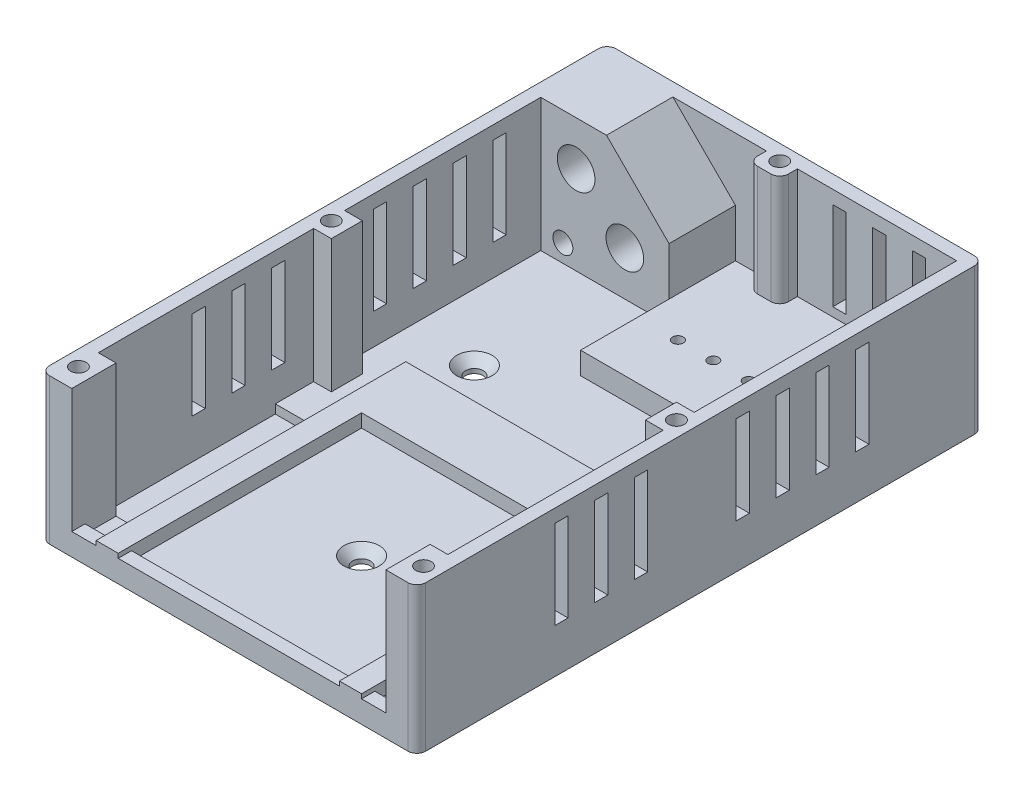
SolidWorks part; units mm, degrees
ref_plane "Front Plane" through (0, 0, 0) normal (0, 0, 1) x (1, 0, 0)
ref_plane "Top Plane" through (0, 0, 0) normal (0, 1, 0) x (1, 0, 0)
ref_plane "Right Plane" through (0, 0, 0) normal (1, 0, 0) x (0, 0, -1)
sketch "Sketch2" plane through (0, 0, 0) normal (0, 1, 0) x (1, 0, 0)
  line L1 (39.5, -62.5) -> (-39.5, -62.5)
  line L2 (39.5, -62.5) -> (39.5, 62.5)
  line L3 (39.5, 62.5) -> (-39.5, 62.5)
  line L4 (-39.5, -62.5) -> (-39.5, 62.5)
  line L5 (39.5, -62.5) -> (-39.5, 62.5) construction
  line L6 (39.5, 62.5) -> (-39.5, -62.5) construction
  point P0 (0, 0)
  dimension "D1" = 79
  dimension "D2" = 125
extrude "Boss-Extrude1" add sketch "Sketch2" along normal blind 3
sketch "Sketch9" plane through (0, 0, 0) normal (0, 1, 0) x (1, 0, 0)
  line L2 (-39.5, 62.5) -> (-39.5, -62.5)
  line L3 (-39.5, -62.5) -> (-42.5, -62.5)
  line L4 (-42.5, 65.5) -> (-42.5, -62.5)
  line L6 (39.5, 62.5) -> (39.5, -62.5)
  line L7 (39.5, -62.5) -> (42.5, -62.5)
  line L8 (42.5, 65.5) -> (42.5, -62.5)
  line L9 (39.5, 62.5) -> (-39.5, 62.5)
  line L11 (42.5, 65.5) -> (-42.5, 65.5)
  dimension "D1" = 3
  dimension "D2" = 3
  dimension "D3" = 3
sketch "Sketch3" plane through (0, 3, 0) normal (0, 1, 0) x (1, 0, 0)
  line L0 (0, -62.5) -> (0, 62.5) construction
  line L1 (-39.5, -62.5) -> (39.5, -62.5) construction
  line L2 (39.5, 62.5) -> (-39.5, 62.5) construction
  line L4 (30, -62.5) -> (-30, -62.5)
  line L5 (30, -62.5) -> (30, 7.5)
  line L6 (30, 7.5) -> (-30, 7.5)
  line L7 (-30, -62.5) -> (-30, 7.5)
  line L8 (30, -62.5) -> (-30, 7.5) construction
  line L9 (30, 7.5) -> (-30, -62.5) construction
  point P6 (0, -27.5)
  dimension "D1" = 60
  dimension "D2" = 70
extrude "support" add sketch "Sketch3" along normal blind 3
sketch "Sketch4" plane through (0, 6, 0) normal (0, 1, 0) x (1, 0, 0)
  line L0 (-30, -62.5) -> (30, -62.5) construction
  line L1 (-25, -62.5) -> (25, -62.5)
  line L2 (-25, -62.5) -> (-25, -7.5)
  line L3 (-25, -7.5) -> (25, -7.5)
  line L4 (25, -62.5) -> (25, -7.5)
  line L5 (30, 7.5) -> (-30, 7.5) construction
  line L6 (30, -62.5) -> (30, 7.5) construction
  line L7 (-30, 7.5) -> (-30, -62.5) construction
  dimension "D1" = 15
  dimension "D2" = 5
  dimension "D3" = 5
extrude "remove plastic" cut sketch "Sketch4" against normal blind 3
sketch "Sketch5" plane through (0, 3, 0) normal (0, 1, 0) x (1, 0, 0)
  line L1 (-10.5, 62.5) -> (39.5, 62.5)
  line L2 (-10.5, 62.5) -> (-10.5, 27.5)
  line L3 (-10.5, 27.5) -> (39.5, 27.5)
  line L4 (39.5, 62.5) -> (39.5, 27.5)
  line L5 (39.5, -62.5) -> (39.5, 62.5) construction
  line L7 (30, -62.5) -> (39.5, -62.5) construction
  line L8 (39.5, 62.5) -> (-39.5, 62.5) construction
  dimension "D1" = 50
  dimension "D3" = 90
extrude "Boss-Extrude3" add sketch "Sketch5" along normal blind 5
sketch "Sketch6" plane through (0, 8, 0) normal (0, 1, 0) x (1, 0, 0)
  line L0 (-10.5, 40.5) -> (39.5, 40.5) construction
  line L3 (14.5, 62.5) -> (14.5, 27.5) construction
  line L4 (39.5, 62.5) -> (-10.5, 62.5) construction
  line L5 (-10.5, 27.5) -> (39.5, 27.5) construction
  line L8 (-10.5, 27.5) -> (39.5, 27.5) construction
  circle A0 centre (-1.5, 40.5) radius 1.2
  circle A1 centre (6.5, 40.5) radius 1.2
  circle A2 centre (14.5, 40.5) radius 1.2
  circle A3 centre (22.5, 40.5) radius 1.2
  circle A4 centre (30.5, 40.5) radius 1.2
  dimension "D1" = 2.4
  dimension "D2" = 8
  dimension "D3" = 8
  dimension "D4" = 8
  dimension "D5" = 8
  dimension "D6" = 13
extrude "Cut-Extrude2" cut sketch "Sketch6" against normal blind 5 draft 1
sketch "Sketch7" plane through (0, 3, 0) normal (0, 1, 0) x (1, 0, 0)
  line L0 (-39.5, 62.5) -> (-39.5, -62.5) construction
  line L1 (-10.5, 62.5) -> (-39.5, 62.5)
  line L2 (-10.5, 62.5) -> (-10.5, 47.5)
  line L3 (-10.5, 47.5) -> (-39.5, 47.5)
  line L4 (-39.5, 62.5) -> (-39.5, 47.5)
  dimension "D1" = 15
extrude "cable block" add sketch "Sketch7" along normal blind 30
extrude "walls" add sketch "Sketch9" along normal up to surface (33 mm away) up to face at (-25, 33, -55)
sketch "Sketch8" plane through (0, 0, -47.5) normal (0, 0, 1) x (1, 0, 0)
  line L0 (-10.5, 33) -> (-10.5, 8) construction
  line L2 (-39.5, 33) -> (-10.5, 33) construction
  line L4 (-39.5, 3) -> (-10.5, 3) construction
  line L5 (-39.5, 33) -> (-39.5, 3) construction
  circle A0 centre (-20.5, 13) radius 4.25
  circle A1 centre (-34.5, 7) radius 2.25
  circle A2 centre (-31.5, 23) radius 4.25
  dimension "D1" = 8.5
  dimension "D2" = 4.5
  dimension "D3" = 10
  dimension "D8" = 10
  dimension "D4" = 8
  dimension "D5" = 10
  dimension "D6" = 5
  dimension "D7" = 4
extrude "cable holes round" cut sketch "Sketch8" against normal blind 31
sketch "Sketch10" plane through (0, 3, 0) normal (0, 1, 0) x (1, 0, 0)
  line L0 (0, -62.5) -> (0, -7.5) construction
  line L1 (-25, -62.5) -> (25, -62.5) construction
  line L2 (25, -7.5) -> (-25, -7.5) construction
  line L3 (-35.5, -62.5) -> (35.5, -62.5) construction
  line L4 (39.5, -62.5) -> (39.5, 27.5) construction
  line L5 (-39.5, -62.5) -> (-35.5, -62.5)
  line L6 (-39.5, -62.5) -> (-39.5, -52.5)
  line L7 (-39.5, -52.5) -> (-35.5, -52.5)
  line L8 (-35.5, -62.5) -> (-35.5, -52.5)
  line L9 (35.5, -62.5) -> (39.5, -62.5)
  line L10 (35.5, -62.5) -> (35.5, -52.5)
  line L11 (35.5, -52.5) -> (39.5, -52.5)
  line L12 (39.5, -62.5) -> (39.5, -52.5)
  dimension "D1" = 71
  dimension "D2" = 10
  dimension "D3" = 10
extrude "Lid screw posts front" add sketch "Sketch10" along normal up to surface (30 mm away) up to face at (-2.1, 33, -10.1)
sketch "Sketch11" plane through (0, 0, -62.5) normal (0, 0, 1) x (1, 0, 0)
  line L0 (14.5, 18) -> (32.5, 18)
  line L1 (39.5, 33) -> (39.5, 8) construction
  line L2 (14.5, 8) -> (32.5, 8)
  line L5 (39.5, 8) -> (-10.5, 8) construction
  arc A0 (14.5, 18) -> (14.5, 8) centre (14.5, 13) ccw
  arc A1 (32.5, 8) -> (32.5, 18) centre (32.5, 13) ccw
  dimension "D1" = 7
  dimension "D2" = 10
  dimension "D3" = 10
  dimension "D4" = 18
extrude "Cable cutout" [suppressed] cut sketch "Sketch11" against normal up to surface (3 mm away) up to face at (-27.25, 23, -65.5)
sketch "Sketch12" plane through (0, 0, -47.5) normal (0, 0, 1) x (1, 0, 0)
  line L0 (-24.6421, 33) -> (-10.5, 18.8579)
  line L1 (-39.5, 33) -> (-10.5, 33) construction
  line L2 (-10.5, 33) -> (-10.5, 8) construction
  line L3 (-10.5, 18.8579) -> (-10.5, 33)
  line L4 (-10.5, 33) -> (-24.6421, 33)
  dimension "D1" = 45
  dimension "D2" = 20
extrude "remove Material" cut sketch "Sketch12" against normal up to surface (15 mm away) up to face at (14.5, 20.5, -62.5)
sketch "Sketch13" plane through (0, 3, 0) normal (0, 1, 0) x (1, 0, 0)
  line L0 (-39.5, 47.5) -> (-39.5, -52.5) construction
  line L1 (-39.5, -3.8301) -> (-35.5, -3.8301)
  line L2 (-39.5, -3.8301) -> (-39.5, 3.1699)
  line L3 (-39.5, 3.1699) -> (-35.5, 3.1699)
  line L4 (-35.5, -3.8301) -> (-35.5, 3.1699)
  line L5 (39.5, -52.5) -> (39.5, 27.5) construction
  line L6 (39.5, 3.1699) -> (35.5, 3.1699)
  line L7 (39.5, 3.1699) -> (39.5, -3.8301)
  line L8 (39.5, -3.8301) -> (35.5, -3.8301)
  line L9 (35.5, 3.1699) -> (35.5, -3.8301)
  line L10 (0, -62.5) -> (0, 77.8786) construction
  line L11 (-25, -62.5) -> (25, -62.5) construction
  line L12 (39.5, 62.5) -> (-10.5, 62.5) construction
  line L13 (3.5, 58.5) -> (-3.5, 58.5)
  line L14 (3.5, 58.5) -> (3.5, 62.5)
  line L15 (3.5, 62.5) -> (-3.5, 62.5)
  line L16 (-3.5, 58.5) -> (-3.5, 62.5)
  line L17 (3.5, 58.5) -> (-3.5, 62.5) construction
  line L18 (3.5, 62.5) -> (-3.5, 58.5) construction
  point P19 (0, 60.5)
  dimension "D1" = 4
  dimension "D2" = 7
  dimension "D3" = 7
  dimension "D4" = 7
  dimension "D5" = 4
  dimension "D6" = 7
  dimension "D7" = 7
  dimension "D8" = 4
extrude "Lid screw posts back" add sketch "Sketch13" along normal up to surface (30 mm away) up to face at (-3.5203, 33, 7.7857)
sketch "Sketch14" plane through (0, 33, 0) normal (0, 1, 0) x (1, 0, 0)
  line L0 (-35.5, -62.5) -> (-42.5, -62.5) construction
  line L1 (0, 58.5) -> (0, 65.5) construction
  line L2 (42.5, -62.5) -> (35.5, -62.5) construction
  line L3 (42.5, 65.5) -> (42.5, -62.5) construction
  line L4 (39.5, -3.8301) -> (35.5, -3.8301) construction
  line L5 (-35.5, -3.8301) -> (-39.5, -3.8301) construction
  line L6 (-42.5, -62.5) -> (-42.5, 65.5) construction
  line L7 (3.5, 58.5) -> (-3.5, 58.5) construction
  line L8 (-42.5, 65.5) -> (42.5, 65.5) construction
  circle A0 centre (-39, -57.5) radius 1.75
  circle A1 centre (39, -57.5) radius 1.75
  circle A2 centre (39, -0.3301) radius 1.75
  circle A3 centre (-39, -0.3301) radius 1.75
  circle A4 centre (0, 62) radius 1.75
  dimension "D1" = 3.5
  dimension "D10" = 3.5
  dimension "D2" = 5
  dimension "D3" = 3.5
  dimension "D4" = 5
  dimension "D5" = 3.5
  dimension "D6" = 3.5
  dimension "D7" = 3.5
  dimension "D8" = 3.5
  dimension "D9" = 3.5
extrude "Lid screw holes" cut sketch "Sketch14" against normal blind 25 draft 0.5
sketch "Sketch16" plane through (0, 3, 0) normal (0, 1, 0) x (1, 0, 0)
  line L0 (-30, 7.5) -> (-30, -62.5) construction
  line L1 (-39.5, -52.5) -> (-30, -52.5)
  line L2 (-39.5, -52.5) -> (-39.5, -12.5)
  line L3 (-39.5, -12.5) -> (-30, -12.5)
  line L4 (-30, -52.5) -> (-30, -12.5)
  line L5 (30, -62.5) -> (30, 7.5) construction
  line L6 (39.5, -52.5) -> (30, -52.5)
  line L7 (39.5, -52.5) -> (39.5, -12.5)
  line L8 (39.5, -12.5) -> (30, -12.5)
  line L9 (30, -52.5) -> (30, -12.5)
  dimension "D1" = 20
  dimension "D2" = 20
extrude "Sliders" cut sketch "Sketch16" against normal blind 2
sketch "Sketch17" plane through (0, 0, 62.5) normal (0, 0, 1) x (1, 0, 0)
  line L0 (35.5, 33) -> (35.5, 3) construction
  line L1 (-35.5, 3) -> (35.5, 3)
  line L2 (-35.5, 3) -> (-35.5, 5)
  line L3 (-35.5, 5) -> (35.5, 5)
  line L4 (35.5, 3) -> (35.5, 5)
  dimension "D1" = 2
extrude "Front Lip" add sketch "Sketch17" against normal blind 3
sketch "Sketch19" plane through (42.5, 0, 0) normal (1, 0, 0) x (0, 0, -1)
  line L0 (65.5, 20) -> (13.84, 20) construction
  line L1 (65.5, 33) -> (65.5, 0) construction
  line L2 (39.67, 20) -> (36.67, 20) construction
  line L7 (65.5, 33) -> (-62.5, 33) construction
  line L16 (33.67, 33) -> (33.67, 27.4267) construction
  line L17 (24.67, 33) -> (24.67, 27.4664) construction
  line L18 (39.67, 10) -> (36.67, 10)
  line L19 (36.67, 30) -> (36.67, 10)
  line L20 (39.67, 30) -> (39.67, 10)
  line L21 (39.67, 30) -> (36.67, 30)
  line L22 (27.67, 30) -> (27.67, 10)
  line L23 (27.67, 10) -> (30.67, 10)
  line L24 (30.67, 30) -> (30.67, 10)
  line L25 (27.67, 30) -> (30.67, 30)
  line L26 (21.67, 30) -> (18.67, 30)
  line L27 (21.67, 10) -> (18.67, 10)
  line L28 (18.67, 30) -> (18.67, 10)
  line L29 (21.67, 30) -> (21.67, 10)
  line L30 (15.67, 33) -> (15.67, 27.5061) construction
  line L31 (9.67, 10) -> (12.67, 10)
  line L32 (9.67, 30) -> (9.67, 10)
  line L33 (12.67, 30) -> (12.67, 10)
  line L34 (9.67, 30) -> (12.67, 30)
  line L35 (-0.33, 20.9955) -> (-0.33, 33) construction
  line L36 (-10.33, 10) -> (-13.33, 10)
  line L37 (-13.33, 30) -> (-13.33, 10)
  line L38 (-10.33, 30) -> (-10.33, 10)
  line L39 (-10.33, 30) -> (-13.33, 30)
  line L40 (-16.33, 33) -> (-16.33, 27.6473) construction
  line L41 (-22.33, 10) -> (-19.33, 10)
  line L42 (-19.33, 30) -> (-19.33, 10)
  line L43 (-22.33, 30) -> (-22.33, 10)
  line L44 (-22.33, 30) -> (-19.33, 30)
  line L45 (-25.33, 33) -> (-25.33, 25.5009) construction
  line L46 (-28.33, 10) -> (-31.33, 10)
  line L47 (-31.33, 30) -> (-31.33, 10)
  line L48 (-28.33, 30) -> (-28.33, 10)
  line L49 (-28.33, 30) -> (-31.33, 30)
  dimension "D2" = 62.17
  dimension "D3" = 13
  dimension "D4" = 20
  dimension "D5" = 3
  dimension "D7" = 3
  dimension "D8" = 3
  dimension "D9" = 3
  dimension "D10" = 10
  dimension "D11" = 3
  dimension "D12" = 3
extrude "Vents Sides" cut sketch "Sketch19" against normal up to surface (85 mm away) up to face at (-42.5, 16.5, -1.5)
sketch "Sketch22" plane through (0, 0, -65.5) normal (0, 0, -1) x (-1, 0, 0)
  line L0 (-26.5, 33) -> (-26.5, 27.4554) construction
  line L1 (-32.5, 30) -> (-29.5, 30)
  line L2 (-32.5, 30) -> (-32.5, 10)
  line L3 (-32.5, 10) -> (-29.5, 10)
  line L4 (-29.5, 30) -> (-29.5, 10)
  line L5 (-42.5, 20) -> (42.5, 20) construction
  line L6 (-42.5, 33) -> (-42.5, 0) construction
  line L7 (42.5, 33) -> (42.5, 0) construction
  line L8 (42.5, 33) -> (-42.5, 33) construction
  line L9 (-32.5, 20) -> (-29.5, 20) construction
  line L12 (-17.5, 33) -> (-17.5, 27.965) construction
  line L13 (-20.5, 10) -> (-23.5, 10)
  line L14 (-23.5, 30) -> (-23.5, 10)
  line L15 (-20.5, 30) -> (-20.5, 10)
  line L16 (-20.5, 30) -> (-23.5, 30)
  line L17 (-14.5, 10) -> (-11.5, 10)
  line L18 (-14.5, 30) -> (-14.5, 10)
  line L19 (-11.5, 30) -> (-11.5, 10)
  line L20 (-14.5, 30) -> (-11.5, 30)
  dimension "D1" = 13
  dimension "D2" = 10
  dimension "D3" = 3
  dimension "D4" = 20
  dimension "D5" = 3
  dimension "D6" = 3
extrude "Vents Back" cut sketch "Sketch22" against normal up to surface (3 mm away) up to face at (-10.5284, 20.1716, -62.5)
sketch "Sketch20" plane through (0, 3, 0) normal (0, 1, 0) x (1, 0, 0)
  line L1 (-42.5, -62.5) -> (42.5, -62.5) construction
  line L3 (-39.5, 47.5) -> (-39.5, 3.1699) construction
  line L4 (39.5, 3.1699) -> (39.5, 27.5) construction
  line L5 (-10.5, 27.5) -> (39.5, 27.5) construction
  circle A0 centre (0, -32.5) radius 2
  circle A1 centre (-24.5, 17.5) radius 2
  circle A2 centre (24.5, 17.5) radius 2
  point P6 (0, -62.5)
  dimension "D1" = 4
  dimension "D2" = 30
  dimension "D4" = 15
  dimension "D5" = 15
  dimension "D6" = 10
extrude "Cut-Extrude4" cut sketch "Sketch20" against normal up to surface (3 mm away) up to face at (0, 0, -1.5)
sketch "Sketch21" plane through (0, 3, 0) normal (0, 1, 0) x (1, 0, 0)
  circle A0 centre (-24.5, 17.5) radius 4
  circle A1 centre (0, -32.5) radius 4
  circle A2 centre (24.5, 17.5) radius 4
  dimension "D1" = 8
extrude "Cut-Extrude5" cut sketch "Sketch21" against normal blind 3 draft 45
fillet "Fillet1" radius 2 1 edges at (3.5, 20.5, -58.5) type face fillet first side face at (0, 20.5, -58.5) second side face at (3.5, 20.5, -60.5)
fillet "Fillet2" radius 2 1 edges at (-3.5, 20.5, -58.5) type face fillet first side face at (-3.5, 20.5, -60.5) second side face at (-1, 20.5, -58.5)
fillet "Fillet3" radius 2 1 edges at (42.5, 16.5, 62.5) type face fillet first side face at (0, 11.6875, 62.5) second side face at (42.5, 20, 29.83)
fillet "Fillet4" radius 2 1 edges at (42.5, 16.5, -65.5) type face fillet first side face at (42.5, 20, 29.83) second side face at (13, 20, -65.5)
fillet "Fillet5" radius 2 1 edges at (-42.5, 16.5, -65.5) type face fillet first side face at (13, 20, -65.5) second side face at (-42.5, 20, 29.83)
fillet "Fillet6" radius 2 1 edges at (-42.5, 16.5, 62.5) type face fillet first side face at (-42.5, 20, 29.83) second side face at (-0.25, 11.6875, 62.5)
equation "\"c_outside_width\"= 75mm"
equation "\"c_total_length\"= 80mm"
equation "\"c_inside_width\"= 70mm"
equation "\"wall_thickness\"= 3mm"
equation "\"D1@Sketch2\"=\"c_outside_width\" + \"wall_thickness\" + 1"
equation "\"D1@Boss-Extrude1\"=\"wall_thickness\""
equation "\"c_bottom_support_width\"=60"
equation "\"D1@Sketch3\"=\"c_bottom_support_width\""
equation "\"c_bottom_support_length\"=70"
equation "\"D2@Sketch3\"=\"c_bottom_support_length\""
equation "\"c_bottom_support_height\"= 3mm"
equation "\"D1@support\"=\"c_bottom_support_height\""
equation "\"D1@remove plastic\"=\"c_bottom_support_height\""
equation "\"D1@Sketch9\"=\"wall_thickness\""
equation "\"D2@Sketch9\"=\"wall_thickness\""
equation "\"D3@Sketch9\"=\"wall_thickness\""
equation "\"c__outside_height\"= 34.5mm"
equation "\"c_inside_height\"= 30mm"
equation "\"D1@walls\"=\"c__outside_height\""
equation "\"D1@Sketch10\"=\"c_inside_width\"+1"
equation "\"case_screw_diameter\"=3.5"
equation "\"D1@Sketch14\"=\"case_screw_diameter\""
equation "\"D1@cable block\" = \"c_inside_height\""
